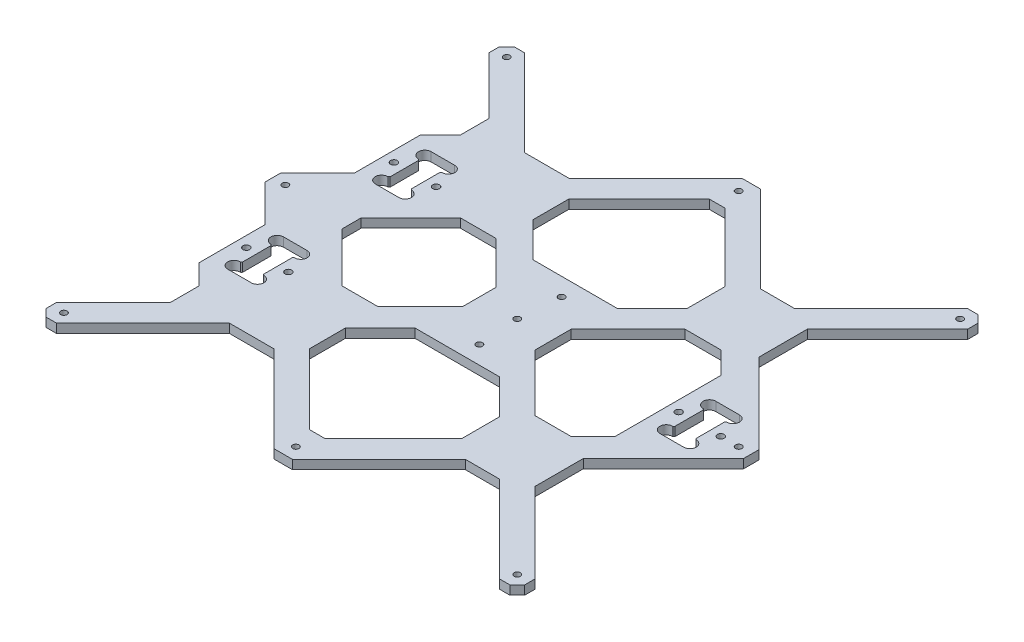
SolidWorks part; units mm, degrees
material "6063-O, Extruded Rod (SS)"
ref_plane "Front Plane" through (0, 0, 0) normal (0, 0, 1) x (1, 0, 0)
ref_plane "Top Plane" through (0, 0, 0) normal (0, 1, 0) x (1, 0, 0)
ref_plane "Right Plane" through (0, 0, 0) normal (1, 0, 0) x (0, 0, -1)
sketch "Sketch2" plane through (0, 0, 0) normal (0, 1, 0) x (1, 0, 0)
  line L0 (162, 177.023) -> (141.977, 157)
  line L1 (141.977, 157) -> (125, 157)
  line L2 (125, 157) -> (101.5, 180.5)
  line L3 (101.5, 189.5) -> (125, 213)
  line L4 (125, 213) -> (141.977, 213)
  line L5 (141.977, 213) -> (162, 192.977)
  line L6 (251.5, 210.0147) -> (240.9853, 220.5294)
  line L7 (240.9853, 220.5294) -> (224.0147, 220.5294)
  line L8 (224.0147, 220.5294) -> (197, 193.5147)
  line L9 (197, 176.4853) -> (224.0147, 149.4706)
  line L10 (224.0147, 149.4706) -> (240.9853, 149.4706)
  line L11 (240.9853, 149.4706) -> (251.5, 159.9853)
  line L12 (184.4001, 296) -> (225.4001, 255)
  line L13 (225.4001, 255) -> (241.5147, 255)
  line L14 (241.5147, 255) -> (282.5147, 296)
  line L15 (282.5147, 296) -> (287.4852, 296)
  line L16 (287.4852, 296) -> (291, 292.4852)
  line L17 (291, 292.4852) -> (291, 287.5147)
  line L18 (291, 287.5147) -> (253, 249.5147)
  line L19 (253, 249.5147) -> (253, 226.667)
  line L20 (253, 226.667) -> (291, 188.667)
  line L21 (291, 188.667) -> (291, 181.333)
  line L22 (291, 181.333) -> (253, 143.333)
  line L23 (253, 143.333) -> (253, 120.4853)
  line L24 (253, 120.4853) -> (291, 82.4853)
  line L25 (291, 82.4853) -> (291, 77.5148)
  line L26 (291, 77.5148) -> (287.4852, 74)
  line L27 (287.4852, 74) -> (282.5147, 74)
  line L28 (282.5147, 74) -> (241.5147, 115)
  line L29 (241.5147, 115) -> (225.4001, 115)
  line L30 (225.4001, 115) -> (184.4001, 74)
  line L31 (184.4001, 74) -> (175.5999, 74)
  line L32 (175.5999, 74) -> (134.5999, 115)
  line L33 (134.5999, 115) -> (113.4853, 115)
  line L34 (113.4853, 115) -> (72.4853, 74)
  line L35 (72.4853, 74) -> (67.5148, 74)
  line L36 (67.5148, 74) -> (64, 77.5148)
  line L37 (64, 77.5148) -> (64, 82.4853)
  line L38 (64, 82.4853) -> (91, 109.4853)
  line L39 (91, 109.4853) -> (91, 123)
  line L40 (91, 123) -> (81.5, 132.5)
  line L41 (81.5, 132.5) -> (81.5, 163.7609)
  line L42 (81.5, 163.7609) -> (64, 181.2609)
  line L43 (64, 188.7391) -> (81.5, 206.2391)
  line L44 (81.5, 206.2391) -> (81.5, 237.5)
  line L45 (81.5, 237.5) -> (91, 247)
  line L46 (91, 247) -> (91, 260.5147)
  line L47 (91, 260.5147) -> (64, 287.5147)
  line L48 (64, 287.5147) -> (64, 292.4852)
  line L49 (64, 292.4852) -> (67.5148, 296)
  line L50 (67.5148, 296) -> (72.4853, 296)
  line L51 (72.4853, 296) -> (113.4853, 255)
  line L52 (113.4853, 255) -> (134.5999, 255)
  line L53 (134.5999, 255) -> (175.5999, 296)
  line L54 (175.5999, 296) -> (184.4001, 296)
  line L55 (143, 246.4158) -> (143, 229.5663)
  line L56 (143, 229.5663) -> (159.5663, 213)
  line L57 (159.5663, 213) -> (199.5147, 213)
  line L58 (199.5147, 213) -> (216, 229.4853)
  line L59 (216, 229.4853) -> (216, 247.4296)
  line L60 (216, 247.4296) -> (183.6826, 279.747)
  line L61 (183.6826, 279.747) -> (176.3174, 279.7332)
  line L62 (176.3174, 279.7332) -> (143, 246.4158)
  line L63 (143, 123.5842) -> (143, 140.4337)
  line L64 (143, 140.4337) -> (159.5663, 157)
  line L65 (159.5663, 157) -> (199.5147, 157)
  line L66 (199.5147, 157) -> (216, 140.5147)
  line L67 (216, 140.5147) -> (216, 122.5704)
  line L68 (216, 122.5704) -> (183.6826, 90.253)
  line L69 (183.6826, 90.253) -> (176.3174, 90.2668)
  line L70 (176.3174, 90.2668) -> (143, 123.5842)
  line L71 (101.5, 226.75) -> (101.5, 213.25)
  line L72 (271.5, 191.75) -> (271.5, 178.25)
  line L73 (101.5, 156.75) -> (101.5, 143.25)
  line L74 (91.5, 226.75) -> (91.5, 213.25)
  line L75 (261.5, 191.75) -> (261.5, 178.25)
  line L76 (91.5, 156.75) -> (91.5, 143.25)
  line L77 (93.6792, 358.4107) -> (93.6792, 347.8262)
  line L78 (93.6792, 347.8262) -> (93.9406, 345.7354)
  line L79 (93.9406, 345.7354) -> (94.4633, 344.2327)
  line L80 (94.4633, 344.2327) -> (95.182, 343.1873)
  line L81 (95.182, 343.1873) -> (96.1846, 341.9648)
  line L82 (96.1846, 341.9648) -> (97.8105, 341.4329)
  line L83 (97.8105, 341.4329) -> (99.6248, 341.0966)
  line L84 (99.6248, 341.0966) -> (101.977, 341.3579)
  line L85 (101.977, 341.3579) -> (104.0024, 342.4033)
  line L86 (104.0024, 342.4033) -> (105.1131, 344.2327)
  line L87 (105.1131, 344.2327) -> (105.5705, 346.7155)
  line L88 (105.5705, 346.7155) -> (105.5705, 349.1983)
  line L89 (105.5705, 349.1983) -> (105.5705, 358.4107)
  line L90 (79.8932, 349.3289) -> (80.0892, 349.3289)
  line L91 (80.0892, 349.3289) -> (81.0039, 348.8063)
  line L92 (81.0039, 348.8063) -> (82.0493, 347.4342)
  line L93 (82.0493, 347.4342) -> (86.4922, 341.0966)
  line L94 (73.5556, 341.1619) -> (73.5556, 358.4107)
  line L95 (73.5556, 358.4107) -> (80.6119, 358.4107)
  line L96 (80.6119, 358.4107) -> (82.768, 357.7574)
  line L97 (82.768, 357.7574) -> (83.8134, 356.7773)
  line L98 (83.8134, 356.7773) -> (84.5321, 355.4706)
  line L99 (84.5321, 355.4706) -> (84.8588, 353.7065)
  line L100 (84.8588, 353.7065) -> (84.5321, 352.0078)
  line L101 (84.5321, 352.0078) -> (83.6827, 350.5703)
  line L102 (83.6827, 350.5703) -> (82.5067, 349.8517)
  line L103 (82.5067, 349.8517) -> (81.3306, 349.525)
  line L104 (81.3306, 349.525) -> (79.8932, 349.3289)
  line L105 (79.8932, 349.3289) -> (78.1291, 349.3289)
  line L106 (78.1291, 349.3289) -> (73.5556, 349.3289)
  line L107 (113.0897, 345.4442) -> (114.2004, 343.4842)
  line L108 (114.2004, 343.4842) -> (116.6178, 341.8507)
  line L109 (116.6178, 341.8507) -> (118.9699, 341.1974)
  line L110 (118.9699, 341.1974) -> (122.4328, 341.7201)
  line L111 (122.4328, 341.7201) -> (124.0662, 343.0268)
  line L112 (124.0662, 343.0268) -> (125.2422, 345.1176)
  line L113 (125.2422, 345.1176) -> (125.2422, 346.359)
  line L114 (125.2422, 346.359) -> (124.9156, 347.4697)
  line L115 (124.9156, 347.4697) -> (123.7395, 348.7764)
  line L116 (123.7395, 348.7764) -> (122.5635, 349.2991)
  line L117 (122.5635, 349.2991) -> (116.7485, 351.0632)
  line L118 (116.7485, 351.0632) -> (115.0497, 352.1739)
  line L119 (115.0497, 352.1739) -> (114.0044, 353.4153)
  line L120 (114.0044, 353.4153) -> (113.8737, 354.5914)
  line L121 (113.8737, 354.5914) -> (114.135, 356.3554)
  line L122 (114.135, 356.3554) -> (115.3764, 357.6622)
  line L123 (115.3764, 357.6622) -> (117.4672, 358.4462)
  line L124 (117.4672, 358.4462) -> (120.0807, 358.5769)
  line L125 (120.0807, 358.5769) -> (122.8248, 357.8582)
  line L126 (122.8248, 357.8582) -> (123.9355, 356.8128)
  line L127 (123.9355, 356.8128) -> (124.3929, 355.5714)
  line L128 (130.9954, 341.0312) -> (137.9864, 358.5414)
  line L129 (137.9864, 358.5414) -> (139.0972, 358.5414)
  line L130 (139.0972, 358.5414) -> (145.9575, 341.0312)
  line L131 (143.9343, 346.1951) -> (133.0803, 346.1927)
  line L132 (55, 341.1619) -> (55, 358.4107)
  line L133 (55, 358.4107) -> (62.0563, 358.4107)
  line L134 (62.0563, 358.4107) -> (64.2125, 357.7574)
  line L135 (64.2125, 357.7574) -> (65.2578, 356.7773)
  line L136 (65.2578, 356.7773) -> (65.9765, 355.4706)
  line L137 (65.9765, 355.4706) -> (66.3032, 353.7065)
  line L138 (66.3032, 353.7065) -> (65.9765, 352.0078)
  line L139 (65.9765, 352.0078) -> (65.1272, 350.5703)
  line L140 (65.1272, 350.5703) -> (63.9511, 349.8517)
  line L141 (63.9511, 349.8517) -> (62.7751, 349.525)
  line L142 (62.7751, 349.525) -> (61.3376, 349.3289)
  line L143 (61.3376, 349.3289) -> (59.5735, 349.3289)
  line L144 (59.5735, 349.3289) -> (55, 349.3289)
  line L145 (251.5, 210.0147) -> (251.5, 159.9853)
  line L146 (197, 193.5147) -> (197, 176.4853)
  line L147 (64, 188.7391) -> (64, 181.2609)
  line L148 (101.5, 189.5) -> (101.5, 180.5)
  line L149 (162, 192.977) -> (162, 177.023)
  line L150 (102.1, 142.75) -> (102, 142.75)
  line L151 (272.1, 177.75) -> (272, 177.75)
  line L152 (102.1, 212.75) -> (102, 212.75)
  line L153 (90.9, 142.75) -> (91, 142.75)
  line L154 (260.9, 177.75) -> (261, 177.75)
  line L155 (90.9, 212.75) -> (91, 212.75)
  line L156 (102, 142.75) -> (101.5, 143.25)
  line L157 (272, 177.75) -> (271.5, 178.25)
  line L158 (102, 212.75) -> (101.5, 213.25)
  line L159 (91, 142.75) -> (91.5, 143.25)
  line L160 (261, 177.75) -> (261.5, 178.25)
  line L161 (91, 212.75) -> (91.5, 213.25)
  line L162 (102.1, 157.25) -> (102, 157.25)
  line L163 (272.1, 192.25) -> (272, 192.25)
  line L164 (102.1, 227.25) -> (102, 227.25)
  line L165 (90.9, 157.25) -> (91, 157.25)
  line L166 (260.9, 192.25) -> (261, 192.25)
  line L167 (90.9, 227.25) -> (91, 227.25)
  line L168 (101.5, 156.75) -> (102, 157.25)
  line L169 (271.5, 191.75) -> (272, 192.25)
  line L170 (101.5, 226.75) -> (102, 227.25)
  line L171 (91.5, 156.75) -> (91, 157.25)
  line L172 (261.5, 191.75) -> (261, 192.25)
  line L173 (91.5, 226.75) -> (91, 227.25)
  line L174 (90.9, 163.25) -> (102.1, 163.25)
  line L175 (260.9, 198.25) -> (272.1, 198.25)
  line L176 (90.9, 233.25) -> (102.1, 233.25)
  line L177 (90.9, 136.75) -> (102.1, 136.75)
  line L178 (260.9, 171.75) -> (272.1, 171.75)
  line L179 (90.9, 206.75) -> (102.1, 206.75)
  arc A0 (102.1, 206.75) -> (102.1, 212.75) centre (102.1, 209.75) ccw
  arc A1 (272.1, 171.75) -> (272.1, 177.75) centre (272.1, 174.75) ccw
  arc A2 (102.1, 136.75) -> (102.1, 142.75) centre (102.1, 139.75) ccw
  arc A3 (90.9, 142.75) -> (90.9, 136.75) centre (90.9, 139.75) ccw
  arc A4 (90.9, 212.75) -> (90.9, 206.75) centre (90.9, 209.75) ccw
  arc A5 (260.9, 177.75) -> (260.9, 171.75) centre (260.9, 174.75) ccw
  arc A6 (102.1, 157.25) -> (102.1, 163.25) centre (102.1, 160.25) ccw
  arc A7 (102.1, 227.25) -> (102.1, 233.25) centre (102.1, 230.25) ccw
  arc A8 (272.1, 192.25) -> (272.1, 198.25) centre (272.1, 195.25) ccw
  arc A9 (90.9, 163.25) -> (90.9, 157.25) centre (90.9, 160.25) ccw
  arc A10 (260.9, 198.25) -> (260.9, 192.25) centre (260.9, 195.25) ccw
  arc A11 (90.9, 233.25) -> (90.9, 227.25) centre (90.9, 230.25) ccw
  circle A12 centre (318.6, 4.9) radius 2.55
  circle A13 centre (318.6, 28.1) radius 2.55
  circle A14 centre (295.4, 28.1) radius 2.55
  circle A15 centre (295.4, 4.9) radius 2.55
  circle A16 centre (281.6, 4.9) radius 2.55
  circle A17 centre (258.4, 4.9) radius 2.55
  circle A18 centre (258.4, 28.1) radius 2.55
  circle A19 centre (281.6, 28.1) radius 2.55
  circle A20 centre (111.6, 4.9) radius 2.55
  circle A21 centre (111.6, 28.1) radius 2.55
  circle A22 centre (88.4, 28.1) radius 2.55
  circle A23 centre (88.4, 4.9) radius 2.55
  circle A24 centre (74.6, 4.9) radius 2.55
  circle A25 centre (74.6, 28.1) radius 2.55
  circle A26 centre (51.4, 28.1) radius 2.55
  circle A27 centre (51.4, 4.9) radius 2.55
  circle A28 centre (360, 39.8) radius 1.5
  circle A29 centre (10, 39.8) radius 1.5
  circle A30 centre (340, 359.8) radius 1.5
  circle A31 centre (30, 39.8) radius 1.5
  circle A32 centre (42.9, 67.8) radius 1.5
  circle A33 centre (340, 39.8) radius 1.5
  circle A34 centre (10, 359.8) radius 1.5
  circle A35 centre (350, 19.8) radius 1.5
  circle A36 centre (47, 99.8) radius 1.5
  circle A37 centre (3.7, 181.1) radius 1.5
  circle A38 centre (20, 19.8) radius 1.5
  circle A39 centre (4.9, 67.8) radius 1.5
  circle A40 centre (360, 359.8) radius 1.5
  circle A41 centre (42.9, 161.8) radius 1.5
  circle A42 centre (3.7, 99.8) radius 1.5
  circle A43 centre (30, 359.8) radius 1.5
  circle A44 centre (47, 174.7) radius 1.5
  circle A45 centre (4.9, 161.8) radius 1.5
  circle A46 centre (46.5, 269.3) radius 1.5
  circle A47 centre (15, 247.8) radius 1.5
  circle A48 centre (3.5, 269.3) radius 1.5
  circle A49 centre (15, 290.8) radius 1.5
  circle A50 centre (180, 80) radius 1.5
  circle A51 centre (180, 290) radius 1.5
  circle A52 centre (285, 80) radius 1.5
  circle A53 centre (70, 290) radius 1.5
  circle A54 centre (285, 290) radius 1.5
  circle A55 centre (70, 185) radius 1.5
  circle A56 centre (180, 185) radius 1.5
  circle A57 centre (285, 185) radius 1.5
  circle A58 centre (256.5, 185) radius 1.6
  circle A59 centre (276.5, 185) radius 1.6
  circle A60 centre (106.5, 220) radius 1.6
  circle A61 centre (106.5, 150) radius 1.6
  circle A62 centre (86.5, 220) radius 1.6
  circle A63 centre (86.5, 150) radius 1.6
  circle A64 centre (70, 80) radius 1.5
  circle A65 centre (181.5, 165.5) radius 1.5
  circle A66 centre (181.5, 204.5) radius 1.5
  circle A67 centre (40, 7) radius 1.6
  circle A68 centre (331, 7) radius 1.6
  circle A69 centre (343, 7) radius 1.6
  circle A70 centre (120, 13) radius 1.6
  circle A71 centre (120, 4) radius 1.6
  circle A72 centre (230, 13) radius 1.6
  circle A73 centre (230, 4) radius 1.6
  circle A74 centre (333.4, 205) radius 2.1
  circle A75 centre (333.4, 88) radius 2.1
  circle A76 centre (26, 7) radius 1.6
  circle A77 centre (153, 13) radius 1.6
  circle A78 centre (153, 4) radius 1.6
  spline S0 degree 2 poles (5, 370) (2.5, 367.5) (0, 365) knots 1472.868668 1472.868668 1472.868668 1479.939736 1479.939736 1479.939736
  spline S1 degree 2 poles (365, 370) (185, 370) (5, 370) knots 1112.868668 1112.868668 1112.868668 1472.868668 1472.868668 1472.868668
  spline S2 degree 2 poles (370, 365) (367.5, 367.5) (365, 370) knots 1105.7976 1105.7976 1105.7976 1112.868668 1112.868668 1112.868668
  spline S3 degree 2 poles (370, 5) (370, 185) (370, 365) knots 745.7976 745.7976 745.7976 1105.7976 1105.7976 1105.7976
  spline S4 degree 2 poles (365, 0) (367.5, 2.5) (370, 5) knots 738.726533 738.726533 738.726533 745.7976 745.7976 745.7976
  spline S5 degree 2 poles (345, 0) (355, 0) (365, 0) knots 718.726533 718.726533 718.726533 738.726533 738.726533 738.726533
  spline S6 degree 2 poles (341, 4) (343, 2) (345, 0) knots 710.241251 710.241251 710.241251 718.726533 718.726533 718.726533
  spline S7 degree 2 poles (333, 4) (337, 4) (341, 4) knots 704.241251 704.241251 704.241251 710.241251 710.241251 710.241251
  spline S8 degree 2 poles (329, 0) (331, 2) (333, 4) knots 698.584397 698.584397 698.584397 704.241251 704.241251 704.241251
  spline S9 degree 2 poles (151, 0) (240, 0) (329, 0) knots 507.584397 507.584397 507.584397 698.584397 698.584397 698.584397
  spline S10 degree 2 poles (146, 5) (148.5, 2.5) (151, 0) knots 501.927543 501.927543 501.927543 507.584397 507.584397 507.584397
  spline S11 degree 2 poles (127, 5) (136.5, 5) (146, 5) knots 487.927543 487.927543 487.927543 501.927543 501.927543 501.927543
  spline S12 degree 2 poles (122, 0) (124.5, 2.5) (127, 5) knots 482.270688 482.270688 482.270688 487.927543 487.927543 487.927543
  spline S13 degree 2 poles (41, 0) (81.5, 0) (122, 0) knots 407.270688 407.270688 407.270688 482.270688 482.270688 482.270688
  spline S14 degree 2 poles (37, 4) (39, 2) (41, 0) knots 401.613834 401.613834 401.613834 407.270688 407.270688 407.270688
  spline S15 degree 2 poles (29, 4) (33, 4) (37, 4) knots 395.613834 395.613834 395.613834 401.613834 401.613834 401.613834
  spline S16 degree 2 poles (25, 0) (27, 2) (29, 4) knots 387.128553 387.128553 387.128553 395.613834 395.613834 395.613834
  spline S17 degree 2 poles (5, 0) (15, 0) (25, 0) knots 367.128553 367.128553 367.128553 387.128553 387.128553 387.128553
  spline S18 degree 2 poles (0, 5) (2.5, 2.5) (5, 0) knots 360.191742 360.191742 360.191742 367.128553 367.128553 367.128553
  spline S19 degree 2 poles (0, 365) (0, 185) (0, 5) knots 0 0 0 360.191742 360.191742 360.191742
  spline S20 degree 2 poles (93, 31.5) (100, 31.5) (107, 31.5) knots 1110.421356 1110.421356 1110.421356 1117.046356 1117.046356 1117.046356
  spline S21 degree 2 poles (88, 36.5) (90.5, 34) (93, 31.5) knots 1103.350288 1103.350288 1103.350288 1110.421356 1110.421356 1110.421356
  spline S22 degree 2 poles (83, 36.5) (85.5, 36.5) (88, 36.5) knots 1098.350288 1098.350288 1098.350288 1103.350288 1103.350288 1103.350288
  spline S23 degree 2 poles (73, 46.5) (78, 41.5) (83, 36.5) knots 1084.208153 1084.208153 1084.208153 1098.350288 1098.350288 1098.350288
  spline S24 degree 2 poles (55, 46.5) (64, 46.5) (73, 46.5) knots 1066.208153 1066.208153 1066.208153 1084.208153 1084.208153 1084.208153
  spline S25 degree 2 poles (50, 51.5) (52.5, 49) (55, 46.5) knots 1059.137085 1059.137085 1059.137085 1066.208153 1066.208153 1066.208153
  spline S26 degree 2 poles (50, 325) (50, 188.25) (50, 51.5) knots 787.637085 787.637085 787.637085 1059.137085 1059.137085 1059.137085
  spline S27 degree 2 poles (55, 330) (52.5, 327.5) (50, 325) knots 780.566017 780.566017 780.566017 787.637085 787.637085 787.637085
  spline S28 degree 2 poles (315, 330) (185, 330) (55, 330) knots 520.566017 520.566017 520.566017 780.566017 780.566017 780.566017
  spline S29 degree 2 poles (320, 325) (317.5, 327.5) (315, 330) knots 513.494949 513.494949 513.494949 520.566017 520.566017 520.566017
  spline S30 degree 2 poles (320, 51.5) (320, 188.25) (320, 325) knots 241.994949 241.994949 241.994949 513.494949 513.494949 513.494949
  spline S31 degree 2 poles (315, 46.5) (317.5, 49) (320, 51.5) knots 234.923882 234.923882 234.923882 241.994949 241.994949 241.994949
  spline S32 degree 2 poles (297, 46.5) (306, 46.5) (315, 46.5) knots 216.923882 216.923882 216.923882 234.923882 234.923882 234.923882
  spline S33 degree 2 poles (287, 36.5) (292, 41.5) (297, 46.5) knots 202.781746 202.781746 202.781746 216.923882 216.923882 216.923882
  spline S34 degree 2 poles (282, 36.5) (284.5, 36.5) (287, 36.5) knots 197.781746 197.781746 197.781746 202.781746 202.781746 202.781746
  spline S35 degree 2 poles (277, 31.5) (279.5, 34) (282, 36.5) knots 190.710678 190.710678 190.710678 197.781746 197.781746 197.781746
  spline S36 degree 2 poles (263, 31.5) (264, 31.5) (265, 31.5) (270, 31.5) (275, 31.5) (276, 31.5) (277, 31.5) knots 176.710678 176.710678 176.710678 178.710678 178.710678 188.710678 188.710678 190.710678 190.710678 190.710678
  spline S37 degree 2 poles (258, 36.5) (260.5, 34) (263, 31.5) knots 169.63961 169.63961 169.63961 176.710678 176.710678 176.710678
  spline S38 degree 2 poles (210, 36.5) (211.75, 36.5) (213.5, 36.5) (235.75, 36.5) (258, 36.5) knots 121.63961 121.63961 121.63961 125.13961 125.13961 169.63961 169.63961 169.63961
  spline S39 degree 2 poles (190, 16.5) (200, 26.5) (210, 36.5) knots 93.355339 93.355339 93.355339 121.63961 121.63961 121.63961
  spline S40 degree 2 poles (180, 16.5) (185, 16.5) (190, 16.5) knots 83.355339 83.355339 83.355339 93.355339 93.355339 93.355339
  spline S41 degree 2 poles (160, 36.5) (170, 26.5) (180, 16.5) knots 55.071068 55.071068 55.071068 83.355339 83.355339 83.355339
  spline S42 degree 2 poles (112, 36.5) (134.25, 36.5) (156.5, 36.5) (158.25, 36.5) (160, 36.5) knots 7.071068 7.071068 7.071068 51.571068 51.571068 55.071068 55.071068 55.071068
  spline S43 degree 2 poles (107, 31.5) (109.5, 34) (112, 36.5) knots 0 0 0 7.071068 7.071068 7.071068
extrude "Boss-Extrude2" add sketch "Sketch2" along normal blind 4.25 contours L43 L147 L42 L41 L40 L39 L38 L37 L36 L35 L34 L33 L32 L31 L30 L29 L28 L27 L26 L25 L24 L23 L22 L21 L20 L19 L18 L17 L16 L15 L14 L13 L12 L54 L53 L52 L51 L50 L49 L48 L47 L46 L45 L44 A66 A65 A64 region at (170.1997, 0, -185)
sketch "Sketch3" plane through (0, 4.25, 0) normal (0, 1, 0) x (1, 0, 0)
  line L0 (181.5, 203) -> (181.5, 206) construction
  line L1 (180, 204.5) -> (183, 204.5) construction
  line L2 (180, 165.5) -> (183, 165.5) construction
  circle A0 centre (181.5, 204.5) radius 1.5 construction
  circle A1 centre (181.5, 204.5) radius 1.5 construction
  circle A2 centre (181.5, 165.5) radius 1.5 construction
ref_plane "Plane1" through (181.5, 0, 0) normal (1, 0, 0) x (0, 0, -1)
ref_plane "Plane2" through (0, 0, -165.5) normal (0, 0, 1) x (1, 0, 0)
ref_plane "Plane3" through (0, 0, -204.5) normal (0, 0, -1) x (-1, 0, 0)
ref_axis "Axis1" through (180, 44.6578, -185) along (0, -1, 0)
